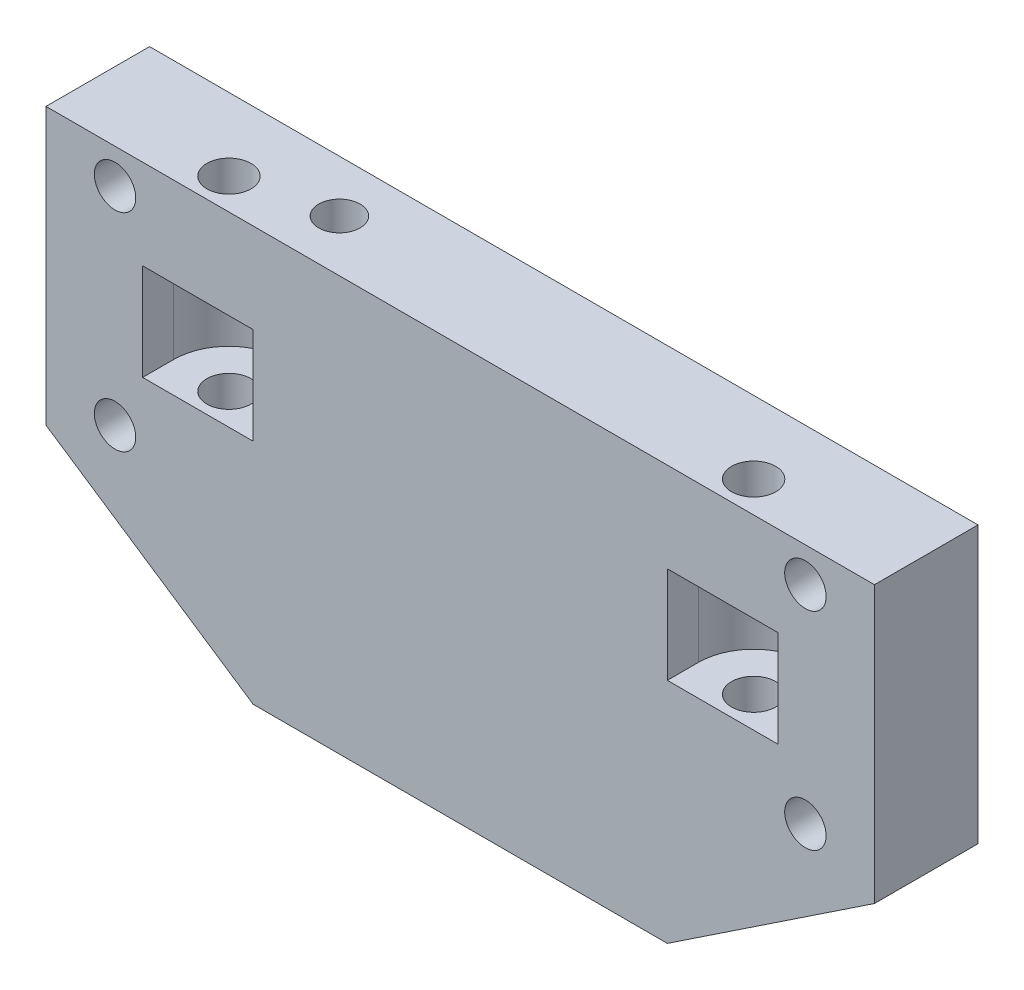
SolidWorks part; units mm, degrees
ref_plane "Front Plane" through (0, 0, 0) normal (0, 0, 1) x (1, 0, 0)
ref_plane "Top Plane" through (0, 0, 0) normal (0, 1, 0) x (1, 0, 0)
ref_plane "Right Plane" through (0, 0, 0) normal (1, 0, 0) x (0, 0, -1)
sketch "Sketch1" plane through (0, 0, 0) normal (0, 0, 1) x (1, 0, 0)
  line L0 (0, 0) -> (19.05, -12.7)
  line L2 (0, 0) -> (0, 25.4)
  line L3 (0, 25.4) -> (76.2, 25.4)
  line L4 (76.2, 0) -> (76.2, 25.4)
  line L5 (19.05, -12.7) -> (57.15, -12.7)
  line L6 (57.15, -12.7) -> (76.2, 0)
  point P7 (57.15, -12.7)
  point P8 (0, 0)
  point P9 (-29.2341, 38.0324)
  point P10 (-0.6581, 0.5881)
  point P11 (19.05, -12.7)
  point P12 (76.2, 25.4)
  point P13 (76.2, -0.5066)
  point P14 (0, 0)
  dimension "D1" = 76.2
  dimension "D2" = 25.4
  dimension "D3" = 12.7
  dimension "D4" = 19.05
  dimension "D5" = 19.05
extrude "Boss-Extrude1" add sketch "Sketch1" along normal blind 9.525
ref_plane "Plane1" through (0, 12.7, 0) normal (0, 1, 0) x (1, 0, 0)
ref_plane "Plane2" through (38.1, 0, 0) normal (1, 0, 0) x (0, 0, -1)
sketch "Sketch2" plane through (0, 0, 9.525) normal (0, 0, 1) x (1, 0, 0)
  line L1 (0, 25.4) -> (0, 0) construction
  circle A0 centre (6.35, 22.225) radius 1.905
  dimension "D1" = 3.81
  dimension "D2" = 22.225
  dimension "D3" = 6.35
extrude "Cut-Extrude1" cut sketch "Sketch2" against normal through all
sketch "Sketch4" plane through (0, 12.7, 0) normal (0, 1, 0) x (1, 0, 0)
  line L7 (76.2, -9.525) -> (0, -9.525) construction
  line L8 (8.89, -6.6675) -> (8.89, -9.525)
  line L9 (19.05, -6.6675) -> (19.05, -9.525)
  line L10 (19.05, -9.525) -> (8.89, -9.525)
  line L11 (0, -9.525) -> (0, 0) construction
  arc A2 (19.05, -6.6675) -> (8.89, -6.6675) centre (13.97, -6.6675) ccw
  dimension "D1" = 10.16
  dimension "D2" = 2.8575
  dimension "D3" = 13.97
extrude "Cut-Extrude2" cut sketch "Sketch4" against normal mid plane 8.89
sketch "Sketch5" plane through (0, 25.4, 0) normal (0, 1, 0) x (1, 0, 0)
  line L0 (76.2, -9.525) -> (0, -9.525) construction
  line L1 (0, -9.525) -> (0, 0) construction
  circle A0 centre (13.97, -6.6675) radius 2.032
  dimension "D3" = 4.064
  dimension "D1" = 2.8575
  dimension "D2" = 13.97
extrude "Cut-Extrude3" cut sketch "Sketch5" against normal blind 28.575
mirror "Mirror1" about plane through (0, 12.7, 0) normal (0, 1, 0) of "Cut-Extrude1"
mirror "Mirror2" about plane through (38.1, 0, 0) normal (1, 0, 0) of "Cut-Extrude3", "Mirror1", "Cut-Extrude1", "Cut-Extrude2"
sketch "Sketch12" plane through (0, 25.4, 0) normal (0, 1, 0) x (1, 0, 0)
  line L0 (0, -9.525) -> (0, 0) construction
  line L1 (22.225, -4.7625) -> (22.225, -9.525) construction
  line L2 (76.2, -9.525) -> (0, -9.525) construction
  line L3 (22.225, -4.7625) -> (22.225, 0) construction
  line L4 (76.2, 0) -> (0, 0) construction
  circle A0 centre (22.225, -4.7625) radius 1.905
  dimension "D2" = 3.81
  dimension "D1" = 22.225
extrude "Cut-Extrude7" cut sketch "Sketch12" against normal blind 9.525
sketch "Sketch13" plane through (0, 0, 0) normal (-1, 0, 0) x (0, 0, 1)
  line L0 (9.525, 25.4) -> (0, 25.4) construction
  line L1 (4.7625, 12.7) -> (0, 12.7) construction
  line L4 (4.7625, 12.7) -> (9.525, 12.7) construction
  circle A0 centre (4.7625, 12.7) radius 1.905
  dimension "D1" = 3.81
  dimension "D2" = 12.7
extrude "Cut-Extrude8" cut sketch "Sketch13" against normal blind 6.35
